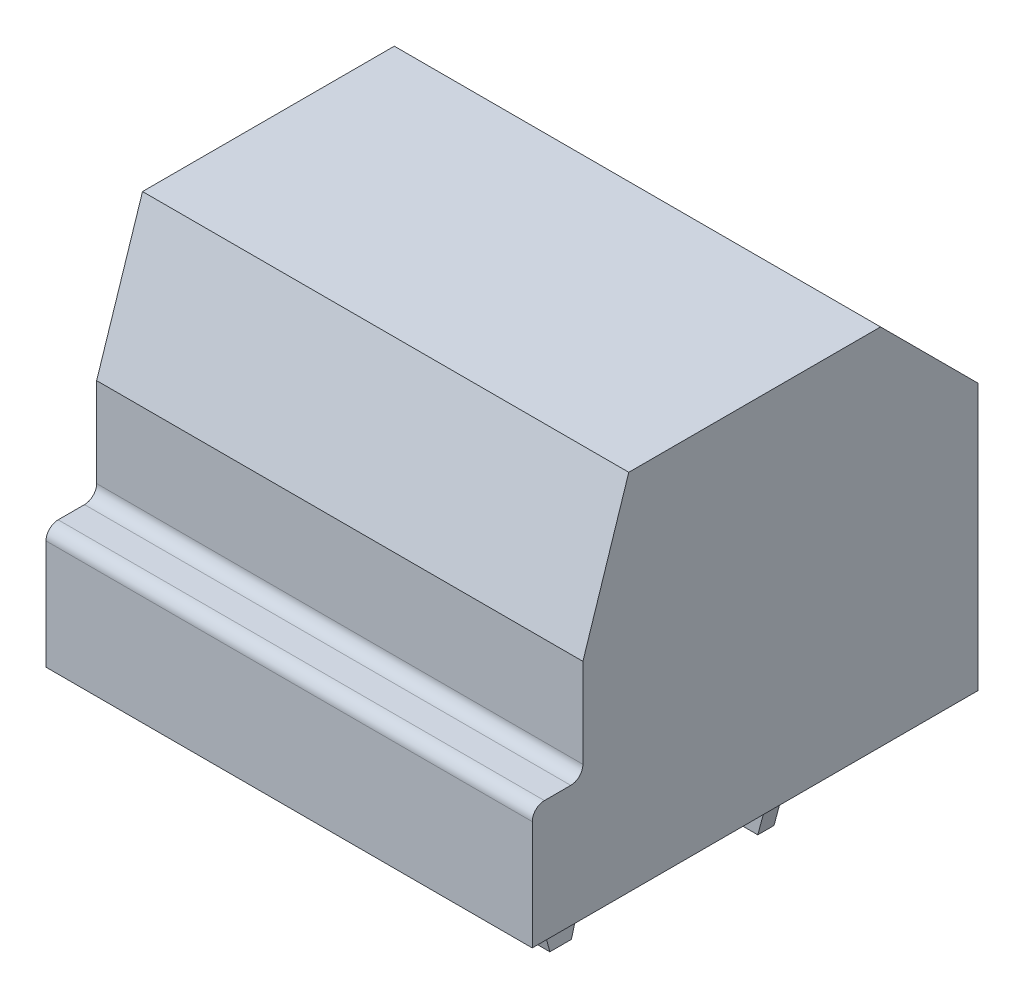
SolidWorks part; units mm, degrees
ref_plane "Front Plane" through (0, 0, 0) normal (0, 0, 1) x (1, 0, 0)
ref_plane "Top Plane" through (0, 0, 0) normal (0, 1, 0) x (1, 0, 0)
ref_plane "Right Plane" through (0, 0, 0) normal (1, 0, 0) x (0, 0, -1)
sketch "Sketch2" plane through (0, 0, 0) normal (1, 0, 0) x (0, 0, -1)
  line L0 (0, 0) -> (11, 0)
  line L5 (11, 0) -> (11, 6.5709)
  line L6 (11, 6.5709) -> (8.5958, 8.975)
  line L7 (8.5958, 8.975) -> (2.3818, 8.975)
  line L8 (2.3818, 8.975) -> (1.25, 5.5)
  line L9 (1.25, 5.5) -> (1.25, 3)
  line L10 (1.25, 3) -> (0, 3)
  line L11 (0, 3) -> (0, 0)
  dimension "D1" = 11
  dimension "D2" = 6.214
  dimension "D3" = 3.4
  dimension "D4" = 2.5
  dimension "D5" = 3
  dimension "D6" = 1.25
extrude "Boss-Extrude2" add sketch "Sketch2" along normal blind 12
sketch "Sketch3" plane through (0, 0, 0) normal (0, -1, 0) x (1, 0, 0)
  line L0 (9.5, -3) -> (12, -3) construction
  line L5 (9.3, -3.4) -> (9.7, -3.4)
  line L6 (9.3, -3.4) -> (9.3, -2.6)
  line L7 (9.3, -2.6) -> (9.7, -2.6)
  line L8 (9.7, -3.4) -> (9.7, -2.6)
  line L9 (9.3, -3.4) -> (9.7, -2.6) construction
  line L10 (9.3, -2.6) -> (9.7, -3.4) construction
  line L12 (12, 0) -> (12, -11) construction
  line L13 (9.1, -7.8) -> (9.9, -7.8)
  line L14 (9.1, -7.8) -> (9.1, -8.2)
  line L15 (9.1, -8.2) -> (9.9, -8.2)
  line L16 (9.9, -7.8) -> (9.9, -8.2)
  line L17 (9.1, -7.8) -> (9.9, -8.2) construction
  line L18 (9.1, -8.2) -> (9.9, -7.8) construction
  line L19 (9.5, -3) -> (9.5, -8) construction
  line L20 (9.5, -3) -> (9.5, 0) construction
  line L21 (12, 0) -> (0, 0) construction
  point P0 (9.5, -3)
  point P9 (9.5, -8)
  dimension "D1" = 2.5
  dimension "D2" = 0.8
  dimension "D3" = 0.4
  dimension "D4" = 5
  dimension "D5" = 3
extrude "Boss-Extrude3" add sketch "Sketch3" along normal blind 2.6
chamfer "Chamfer1" distance 0.5 angle 15 4 edges at (9.5, -2.6, -2.6) (9.5, -2.6, -3.4) (9.1, -2.6, -8) (9.9, -2.6, -8) first distance on face at (9.5, -1.3, -2.6) first distance on face at (9.5, -1.3, -3.4) first distance on face at (9.1, -1.3, -8) first distance on face at (9.9, -1.3, -8)
pattern_linear "LPattern1" count 3 spacing 3.5 along (-1, 0, 0) of "Boss-Extrude3", "Chamfer1"
sketch "Sketch4" plane through (0, 8.7854, -8.7854) normal (0, 0.7071, -0.7071) x (1, 0, 0)
  line L0 (9.5, -0.2681) -> (9.5, 3.1319) construction
  line L1 (10.75, 2.6819) -> (8.25, 2.6819)
  line L2 (10.75, 2.6819) -> (10.75, 0.1819)
  line L3 (10.75, 0.1819) -> (8.25, 0.1819)
  line L4 (8.25, 2.6819) -> (8.25, 0.1819)
  line L5 (10.75, 2.6819) -> (8.25, 0.1819) construction
  line L6 (10.75, 0.1819) -> (8.25, 2.6819) construction
  line L7 (12, -0.2681) -> (0, -0.2681) construction
  line L8 (12, 3.1319) -> (0, 3.1319) construction
  line L9 (9.5, 1.4319) -> (12, 1.4319) construction
  line L10 (12, 3.1319) -> (12, -0.2681) construction
  point P0 (9.5, 1.4319)
  point P12 (9.5, 1.4319)
  dimension "D1" = 2.5
  dimension "D2" = 2.5
  dimension "D3" = 2.5
extrude "Cut-Extrude1" cut sketch "Sketch4" against normal blind 2
chamfer "Chamfer2" distance 1.1 angle 25 4 edges at (9.5, 5.4749, -9.2676) (10.75, 6.3588, -8.3837) (9.5, 7.2426, -7.4998) (8.25, 6.3588, -8.3837) first distance on face at (9.5, 6.182, -9.9747) first distance on face at (10.75, 7.0659, -9.0908) first distance on face at (9.5, 7.9497, -8.2069) first distance on face at (8.25, 7.0659, -9.0908)
fillet "Fillet1" radius 0.6 8 edges at (10.75, 6.5709, -10.3636) (8.25, 6.5709, -10.3636) (8.25, 8.3387, -8.5958) (10.75, 8.3387, -8.5958) (10.4935, 6.0451, -9.4751) (8.5065, 6.0451, -9.4751) (8.5065, 7.4502, -8.0701) (10.4935, 7.4502, -8.0701)
pattern_linear "LPattern2" count 3 spacing 3.5 along (-1, 0, 0) of "Fillet1", "Chamfer2", "Cut-Extrude1"
fillet "Fillet2" radius 0.3 2 edges at (6, 3, -1.25) (6, 3, 0)
